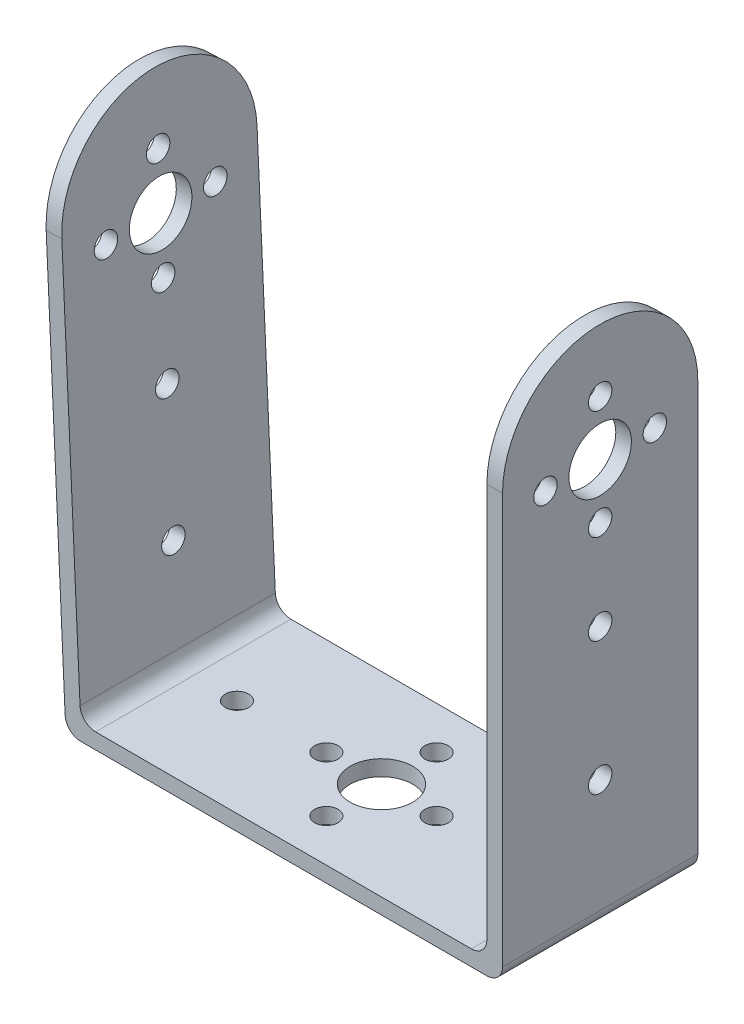
SolidWorks part; units mm, degrees
ref_plane "Front Plane" through (0, 0, 0) normal (0, 0, 1) x (1, 0, 0)
ref_plane "Top Plane" through (0, 0, 0) normal (0, 1, 0) x (1, 0, 0)
ref_plane "Right Plane" through (0, 0, 0) normal (1, 0, 0) x (0, 0, -1)
sketch "Sketch1" plane through (0, 0, 0) normal (0, 0, 1) x (1, 0, 0)
  line L4 (27.9991, 67) -> (25.9991, 67)
  line L17 (-26.0009, 2) -> (-29.0009, 67)
  line L23 (-29.0009, 67) -> (-30.9988, 66.9078)
  line L24 (-30.9988, 66.9078) -> (-27.9107, 0)
  line L25 (-27.9107, 0) -> (-26.0009, 0)
  line L26 (25.9991, 67) -> (25.9991, 2)
  line L27 (25.9991, 2) -> (-26.0009, 2)
  line L28 (27.9991, 67) -> (27.9991, 0)
  line L29 (27.9991, 0) -> (-26.0009, 0)
  point P4 (0, 0)
  dimension "D1" = 2
  dimension "D7" = 2
  dimension "D2" = 55
  dimension "D3" = 2
  dimension "D4" = 65
  dimension "D5" = 52
  dimension "D6" = 2
  dimension "D9" = 90
extrude "Boss-Extrude1" add sketch "Sketch1" against normal blind 25
sketch "Sketch4" plane through (-27.8514, -1.2854, 0) normal (-0.9989, -0.0461, 0) x (0, 0, 1)
  line L0 (-12.5, 1.2868) -> (-12.5, 16.9303) construction
  line L1 (-25, 1.2868) -> (0, 1.2868) construction
  line L2 (-12.5, 16.9303) -> (-12.5, 33.9303) construction
  line L3 (-12.5, 33.9303) -> (-12.5, 52.4303) construction
  line L4 (-25, 68.2658) -> (0, 68.2658) construction
  line L5 (-25, 68.2658) -> (-25, 1.2868) construction
  line L6 (0, 68.2658) -> (0, 1.2868) construction
  line L7 (-25, 55.7658) -> (-25, 68.2658)
  line L8 (-25, 68.2658) -> (0, 68.2658)
  line L9 (0, 68.2658) -> (0, 55.7658)
  circle A0 centre (-12.5, 52.4303) radius 4
  circle A1 centre (-12.5, 52.4303) radius 7 construction
  circle A2 centre (-19.5, 52.4303) radius 1.5
  circle A3 centre (-12.5, 59.4303) radius 1.5
  circle A4 centre (-5.5, 52.4303) radius 1.5
  circle A5 centre (-12.5, 45.4303) radius 1.5
  circle A6 centre (-12.5, 33.9303) radius 1.5
  circle A7 centre (-12.5, 16.9303) radius 1.5
  arc A8 (0, 55.7658) -> (-25, 55.7658) centre (-12.5, 55.7658) ccw
  line M7 (0, 1.2868) -> (0, 68.2658)
  line M8 (0, 68.2658) -> (-25, 68.2658)
  line M9 (-25, 68.2658) -> (-25, 1.2868)
  dimension "D1" = 4
extrude "Cut-Extrude3" cut sketch "Sketch4" against normal blind 2 contours A8 L8 M9 | A8 M7 M8 | A3 | A4 | A2 | A6 | A7 | A5 | A0 region at (-30.8701, 64.1187, -2.7921) region at (-30.8701, 64.1187, -22.2079) region at (-30.2687, 51.0891, -19.5) region at (-30.5914, 58.0816, -12.5) region at (-30.2687, 51.0891, -5.5) region at (-29.4158, 32.6087, -12.5) region at (-28.632, 15.6268, -12.5)
sketch "Sketch5" plane through (27.9991, 0, 0) normal (1, 0, 0) x (0, 0, -1)
  line L0 (12.5, 0) -> (12.5, 16.5) construction
  line L1 (25, 0) -> (0, 0) construction
  line L2 (12.5, 16.5) -> (12.5, 33.5) construction
  line L3 (12.5, 33.5) -> (12.5, 52) construction
  line L4 (25, 67) -> (0, 67) construction
  line L5 (0, 0) -> (0, 67) construction
  line L6 (25, 0) -> (25, 67) construction
  line L7 (0, 54.5) -> (0, 67)
  line L8 (0, 67) -> (25, 67)
  line L9 (25, 67) -> (25, 54.5)
  circle A0 centre (12.5, 52) radius 4
  circle A1 centre (12.5, 52) radius 7 construction
  circle A2 centre (5.5, 52) radius 1.5
  circle A3 centre (12.5, 59) radius 1.5
  circle A4 centre (19.5, 52) radius 1.5
  circle A5 centre (12.5, 45) radius 1.5
  circle A6 centre (12.5, 33.5) radius 1.5
  circle A7 centre (12.5, 16.5) radius 1.5
  arc A8 (25, 54.5) -> (0, 54.5) centre (12.5, 54.5) ccw
  line M10 (0, 67) -> (0, 0)
  line M12 (25, 0) -> (25, 67)
  line M13 (25, 67) -> (0, 67)
  dimension "D1" = 4
extrude "Cut-Extrude4" cut sketch "Sketch5" against normal blind 2 contours A8 L8 M10 | A8 M12 M13 | A3 | A4 | A5 | A2 | A6 | A7 | A0 region at (27.9991, 64.2079, -22.2079) region at (27.9991, 64.2079, -2.7921) region at (27.9991, 52, -12.5) region at (27.9991, 52, -5.5) region at (27.9991, 59, -12.5) region at (27.9991, 52, -19.5) region at (27.9991, 45, -12.5) region at (27.9991, 33.5, -12.5) region at (27.9991, 16.5, -12.5)
sketch "Sketch6" plane through (0, 2, 0) normal (0, 1, 0) x (1, 0, 0)
  line L0 (-0.0009, 0) -> (-0.0009, 25) construction
  line L1 (25.9991, 0) -> (-26.0009, 0) construction
  line L2 (25.9991, 25) -> (-26.0009, 25) construction
  line L3 (-0.0009, 12.5) -> (18.4991, 12.5) construction
  line L4 (-0.0009, 12.5) -> (-18.5009, 12.5) construction
  circle A0 centre (-0.0009, 12.5) radius 4
  circle A1 centre (-0.0009, 12.5) radius 7.0559 construction
  circle A2 centre (-7.0568, 12.5) radius 1.5
  circle A3 centre (-0.0009, 19.5559) radius 1.5
  circle A4 centre (7.055, 12.5) radius 1.5
  circle A5 centre (-0.0009, 5.4441) radius 1.5
  circle A6 centre (18.4991, 12.5) radius 1.5
  circle A7 centre (-18.5009, 12.5) radius 1.5
extrude "Cut-Extrude5" cut sketch "Sketch6" against normal blind 2
fillet "Fillet2" radius 2 4 edges at (-27.9107, 0, -12.5) (-26.0009, 2, -12.5) (25.9991, 2, -12.5) (27.9991, 0, -12.5)
